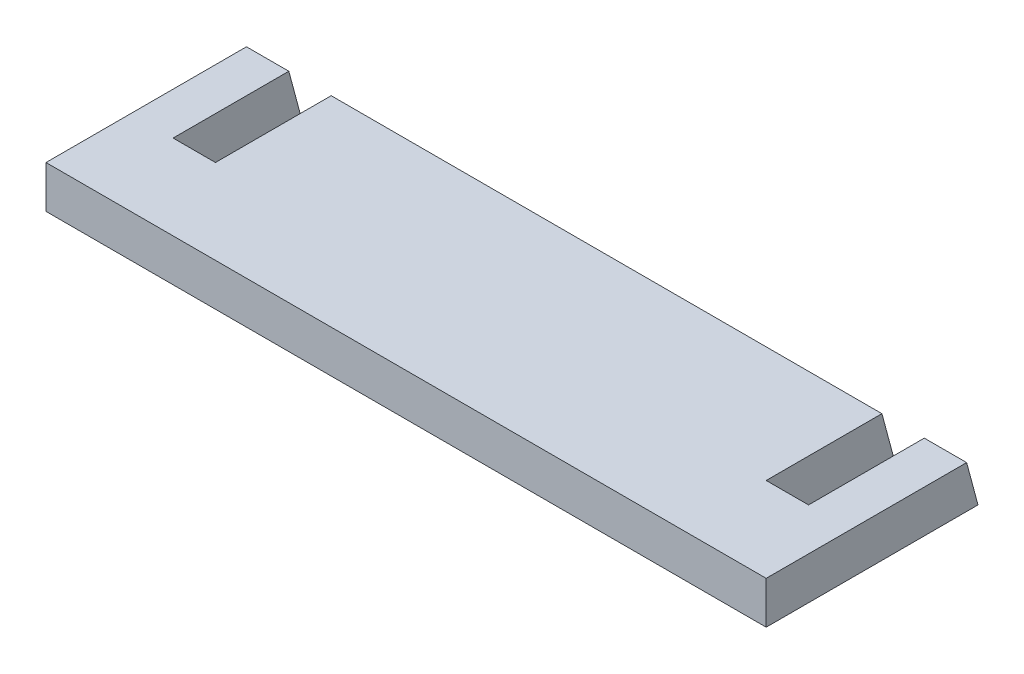
SolidWorks part; units mm, degrees
ref_plane "Front Plane" through (0, 0, 0) normal (0, 0, 1) x (1, 0, 0)
ref_plane "Top Plane" through (0, 0, 0) normal (0, 1, 0) x (1, 0, 0)
ref_plane "Right Plane" through (0, 0, 0) normal (1, 0, 0) x (0, 0, -1)
sketch "Sketch2" plane through (0, 0, 0) normal (0, 1, 0) x (1, 0, 0)
  line L1 (-85, 25) -> (85, 25)
  line L2 (-85, 25) -> (-85, -25)
  line L3 (-85, -25) -> (85, -25)
  line L4 (85, 25) -> (85, -25)
  line L5 (-85, 25) -> (85, -25) construction
  line L6 (-85, -25) -> (85, 25) construction
  point P0 (0, 0)
  dimension "D1" = 170
  dimension "D2" = 50
extrude "Boss-Extrude1" add sketch "Sketch2" along normal blind 10
chamfer "Chamfer1" distance 10 angle 15 1 edges at (0, 10, -25) first distance on face at (0, 5, -25)
sketch "Sketch4" plane through (0, 0, 0) normal (0, 1, 0) x (1, 0, 0)
  line L0 (0, -5) -> (0, 25) construction
  line L1 (85, 25) -> (-85, 25) construction
  line L2 (0, -5) -> (-65, -5) construction
  line L3 (75, -5) -> (75, 25)
  line L4 (-65, -5) -> (-75, -5)
  line L5 (-65, -5) -> (-65, 25)
  line L6 (-65, 25) -> (-75, 25)
  line L7 (-75, -5) -> (-75, 25)
  line L8 (65, 25) -> (75, 25)
  line L9 (65, -5) -> (65, 25)
  line L10 (65, -5) -> (75, -5)
  point P9 (0, 0)
  point P10 (0, 0)
  dimension "D1" = 65
  dimension "D2" = 10
  dimension "D3" = 30
extrude "Cut-Extrude1" cut sketch "Sketch4" along normal blind 10
